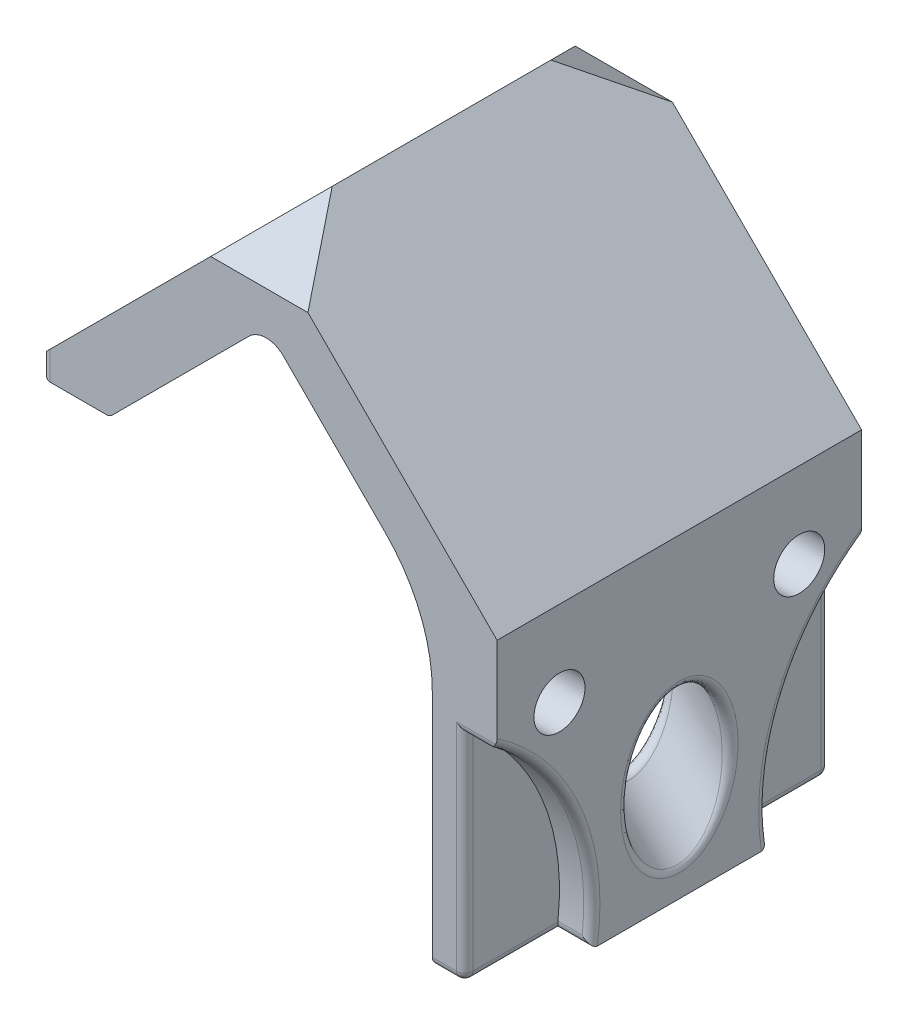
SolidWorks part; units mm, degrees
material "PA 类型 6"
ref_plane "前视基准面" through (0, 0, 0) normal (0, 0, 1) x (1, 0, 0)
ref_plane "上视基准面" through (0, 0, 0) normal (0, 1, 0) x (1, 0, 0)
ref_plane "右视基准面" through (0, 0, 0) normal (1, 0, 0) x (0, 0, -1)
sketch "草图1" plane through (0, 0, 0) normal (0, 0, 1) x (1, 0, 0)
  line L0 (0, 0) -> (144.3086, 0) construction
  line L1 (0, 0) -> (0, 98.9497) construction
  line L4 (14.253, 0) -> (14.253, -19.4462)
  line L5 (14.253, -19.4462) -> (10.253, -19.4462)
  line L6 (10.253, -19.4462) -> (10.253, -0.5962)
  line L7 (10.253, -0.5962) -> (0, 9.6569)
  line L8 (0, 9.6569) -> (-9.6569, 0)
  line L9 (-9.6569, 0) -> (-13.8593, 0)
  line L10 (-13.8593, 0) -> (-13.8593, 1.2423)
  line L11 (-13.8593, 1.2423) -> (-0.4243, 14.6773)
  line L12 (-0.4243, 14.6773) -> (14.253, 0)
  line L13 (-7.1418, 7.9598) -> (-5.4831, 6.3011) construction
  dimension "D1" = 3.85
  dimension "D2" = 3.25
  dimension "D3" = 45
  dimension "D4" = 6.25
  dimension "D5" = 4
  dimension "D6" = 18.85
  dimension "D7" = 14.5
extrude "主结构" add sketch "草图1" along normal blind 22.5
sketch "草图2" plane through (-7.5508, 7.5508, 0) normal (-0.7071, 0.7071, 0) x (0, 0, 1)
  line L0 (22.5, 10.0784) -> (22.5, -8.9216) construction
  line L1 (22.5, 0.5784) -> (0, 0.5784) construction
  line L2 (0, 10.0784) -> (0, -8.9216) construction
  circle A0 centre (11.25, 0.5784) radius 3.125
  dimension "D1" = 6.25
extrude "SMA接口" cut sketch "草图2" against normal through all
sketch "草图3" plane through (14.253, 0, 0) normal (1, 0, 0) x (0, 0, -1)
  line L0 (-22.5, -5.25) -> (0, -5.25) construction
  line L1 (-22.5, -19.4462) -> (-22.5, 0) construction
  line L2 (0, -19.4462) -> (0, 0) construction
  line L3 (-11.25, -5.25) -> (-11.25, -23.4325) construction
  line L4 (-22.5, 0) -> (0, 0) construction
  circle A0 centre (-18.65, -5.25) radius 1.575
  circle A1 centre (-3.85, -5.25) radius 1.575
  dimension "D2" = 3.15
  dimension "D1" = 7.4
  dimension "D3" = 5.25
extrude "侧板接口" cut sketch "草图3" against normal through all
sketch "草图4" plane through (10.253, 0, 0) normal (-1, 0, 0) x (0, 0, 1)
  line L1 (5.4377, -8) -> (7.0254, -5.25)
  line L2 (7.0254, -5.25) -> (5.4377, -2.5)
  line L3 (5.4377, -2.5) -> (2.2623, -2.5)
  line L4 (2.2623, -2.5) -> (0.6746, -5.25)
  line L5 (0.6746, -5.25) -> (2.2623, -8)
  line L6 (2.2623, -8) -> (5.4377, -8)
  line L7 (20.2377, -8) -> (21.8254, -5.25)
  line L8 (21.8254, -5.25) -> (20.2377, -2.5)
  line L9 (20.2377, -2.5) -> (17.0623, -2.5)
  line L10 (17.0623, -2.5) -> (15.4746, -5.25)
  line L11 (15.4746, -5.25) -> (17.0623, -8)
  line L12 (17.0623, -8) -> (20.2377, -8)
  circle A0 centre (3.85, -5.25) radius 2.75 construction
  circle A1 centre (18.65, -5.25) radius 2.75 construction
  circle A2 centre (3.85, -5.25) radius 1.575 construction
  circle A3 centre (18.65, -5.25) radius 1.575 construction
  dimension "D1" = 5.5
extrude "侧板接口-2" cut sketch "草图4" against normal blind 1.25
sketch "造型切除定位-1" plane through (0, 0, 0) normal (0, 0, -1) x (-1, 0, 0)
  line L0 (-2.5757, 11.6773) -> (3.4243, 11.6773)
  line L1 (-14.253, 0) -> (0.4243, 14.6773) construction
  line L2 (0.4243, 14.6773) -> (13.8593, 1.2423) construction
  dimension "D1" = 3
sketch "造型切除定位-2" plane through (-7.5508, 7.5508, 0) normal (-0.7071, 0.7071, 0) x (0, 0, 1)
  line L0 (0, 10.0784) -> (11.25, 10.0784)
  line L1 (22.5, 10.0784) -> (0, 10.0784) construction
  line L2 (0, 10.0784) -> (4.5, 10.0784)
  dimension "D1" = 4.5
ref_plane "中心对称面" through (0, 0, 11.25) normal (0, 0, 1) x (1, 0, 0)
ref_plane "造型切除面定位-1" through (0, 8.0843, -5.3895) normal (0, -0.8321, 0.5547) x (-1, 0, 0)
sketch "草图7" plane through (0, 8.0843, -5.3895) normal (0, -0.8321, 0.5547) x (-1, 0, 0)
  line L0 (0.4243, -11.8857) -> (-2.5757, -6.4774)
  line L1 (-2.5757, -6.4774) -> (3.4243, -6.4774)
  line L2 (3.4243, -6.4774) -> (0.4243, -11.8857)
extrude "造型切除" cut sketch "草图7" against normal through all
mirror "镜向1" about plane through (0, 0, 11.25) normal (0, 0, 1) of "造型切除"
fillet "圆角1" radius 10 1 edges at (10.253, -0.5962, 11.25)
fillet "圆角2" radius 1.5 1 edges at (0, 9.6569, 11.25)
sketch "草图8" plane through (14.253, 0, 0) normal (1, 0, 0) x (0, 0, -1)
  line L0 (-11.25, 15.49) -> (-11.25, -15.49) construction
  circle A0 centre (-30.65, -17.25) radius 14
  circle A1 centre (-18.65, -5.25) radius 1.575 construction
  circle A3 centre (8.15, -17.25) radius 14
  dimension "D1" = 12
  dimension "D2" = 12
extrude "切除-拉伸1" cut sketch "草图8" against normal blind 2
fillet "圆角3" radius 0.5 12 edges at (14.253, -11.8503, 4.7668) (14.253, -11.8503, 17.7332) (13.253, -19.4462, 16.8233) (13.253, -19.4462, 5.6767) (12.253, -19.4462, 2.8383) (12.253, -19.4462, 19.6617) (13.253, -5.8668, 22.5) (12.253, -12.6565, 22.5) (13.253, -5.8668, 0) (12.253, -12.6565, 0) (11.253, -19.4462, 0) (11.253, -19.4462, 22.5)
fillet "圆角4" radius 0.5 9 edges at (-9.3515, 5.7501, 11.25) (-13.8593, 1.2423, 11.25) (-13.8593, 0.6211, 22.5) (-13.8593, 0, 11.25) (-13.8593, 0.6211, 0) (-9.6569, 0, 11.25) (-6.6291, 3.0277, 11.25) (14.253, -9.0156, 11.25) (10.253, -5.0156, 11.25)
